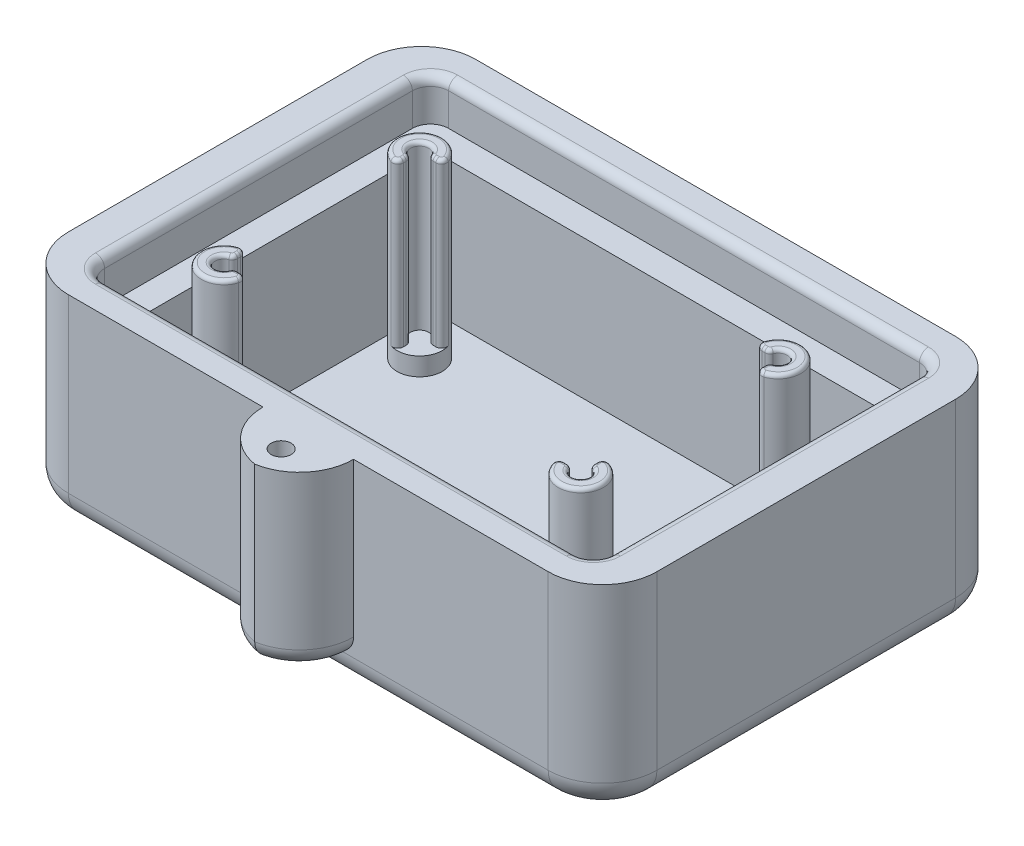
SolidWorks part; units mm, degrees
ref_plane "Front Plane" through (0, 0, 0) normal (0, 0, 1) x (1, 0, 0)
ref_plane "Top Plane" through (0, 0, 0) normal (0, 1, 0) x (1, 0, 0)
ref_plane "Right Plane" through (0, 0, 0) normal (1, 0, 0) x (0, 0, -1)
sketch "Sketch1" plane through (0, 0, 0) normal (0, 1, 0) x (1, 0, 0)
  line L1 (0, 0) -> (82.55, 0)
  line L2 (0, 0) -> (0, 57.15)
  line L3 (0, 57.15) -> (82.55, 57.15)
  line L4 (82.55, 0) -> (82.55, 57.15)
  dimension "D1" = 57.15
  dimension "D2" = 82.55
extrude "Boss-Extrude1" add sketch "Sketch1" along normal blind 27.94
fillet "Fillet2" radius 7.62 4 edges at (82.55, 13.97, -57.15) (82.55, 13.97, 0) (0, 13.97, 0) (0, 13.97, -57.15)
fillet "Fillet3" radius 3.81 8 edges at (80.3182, 0, -54.9182) (82.55, 0, -28.575) (80.3182, 0, -2.2318) (41.275, 0, 0) (2.2318, 0, -2.2318) (0, 0, -28.575) (2.2318, 0, -54.9182) (41.275, 0, -57.15)
sketch "Sketch2" plane through (0, 27.94, 0) normal (0, 1, 0) x (1, 0, 0)
  line L0 (0, 28.575) -> (82.55, 28.575) construction
  line L1 (0, 49.53) -> (0, 7.62) construction
  line L2 (82.55, 7.62) -> (82.55, 49.53) construction
  line L4 (9.525, 8.255) -> (73.025, 8.255)
  line L5 (9.525, 8.255) -> (9.525, 48.895)
  line L6 (9.525, 48.895) -> (73.025, 48.895)
  line L7 (73.025, 8.255) -> (73.025, 48.895)
  line L8 (9.525, 8.255) -> (73.025, 48.895) construction
  line L9 (9.525, 48.895) -> (73.025, 8.255) construction
  point P6 (41.275, 28.575)
  dimension "D1" = 40.64
  dimension "D2" = 63.5
extrude "Cut-Extrude1" cut sketch "Sketch2" against normal blind 25.4
sketch "Sketch7" plane through (0, 27.94, 0) normal (0, 1, 0) x (1, 0, 0)
  line L14 (5.715, 52.705) -> (5.715, 4.445)
  line L15 (5.715, 4.445) -> (76.835, 4.445)
  line L16 (76.835, 4.445) -> (76.835, 52.705)
  line L17 (76.835, 52.705) -> (5.715, 52.705)
  line L18 (5.715, 52.705) -> (5.715, 4.445)
  line L19 (5.715, 4.445) -> (76.835, 4.445)
  line L20 (76.835, 4.445) -> (76.835, 52.705)
  line L21 (76.835, 52.705) -> (5.715, 52.705)
  dimension "D1" = 3.81
sketch "Sketch5" plane through (0, 2.54, 0) normal (0, 1, 0) x (1, 0, 0)
  line L0 (9.525, 48.895) -> (9.525, 8.255) construction
  line L1 (9.525, 8.255) -> (73.025, 8.255) construction
  line L2 (73.025, 48.895) -> (9.525, 48.895) construction
  circle A0 centre (14.605, 42.291) radius 3.175
  circle A1 centre (14.605, 14.859) radius 3.175
  circle A2 centre (64.897, 42.291) radius 3.175
  circle A3 centre (64.8964, 14.605) radius 3.175
  dimension "D5" = 6.35
  dimension "D6" = 6.35
  dimension "D7" = 6.35
  dimension "D8" = 6.35
  dimension "D11" = 6.604
  dimension "D1" = 5.08
  dimension "D2" = 27.432
  dimension "D3" = 27.686
  dimension "D4" = 5.08
  dimension "D9" = 6.604
  dimension "D10" = 50.292
  dimension "D12" = 50.292
sketch "Sketch9" plane through (0, 0, 0) normal (0, 0, 1) x (1, 0, 0)
  line L0 (41.275, 27.94) -> (41.275, 3.81) construction
  line L1 (7.62, 27.94) -> (74.93, 27.94) construction
  line L2 (7.62, 3.81) -> (74.93, 3.81) construction
  line L4 (47.625, 27.94) -> (34.925, 27.94)
  line L5 (47.625, 27.94) -> (47.625, 3.81)
  line L6 (47.625, 3.81) -> (34.925, 3.81)
  line L7 (34.925, 27.94) -> (34.925, 3.81)
  line L8 (47.625, 27.94) -> (34.925, 3.81) construction
  line L9 (47.625, 3.81) -> (34.925, 27.94) construction
  point P6 (41.275, 15.875)
  dimension "D1" = 12.7
extrude "Boss-Extrude5" add sketch "Sketch9" along normal blind 7.62
fillet "Fillet10" radius 7.62 2 edges at (47.625, 15.875, 7.62) (34.925, 15.875, 7.62)
extrude "Cut-Extrude4" cut sketch "Sketch7" against normal blind 5.842
fillet "Fillet12" radius 2.54 4 edges at (76.835, 25.019, -52.705) (76.835, 25.019, -4.445) (5.715, 25.019, -52.705) (5.715, 25.019, -4.445)
fillet "Fillet13" radius 1.27 8 edges at (6.4589, 27.94, -5.1889) (5.715, 27.94, -28.575) (6.4589, 27.94, -51.9611) (41.275, 27.94, -52.705) (76.0911, 27.94, -51.9611) (76.835, 27.94, -28.575) (76.0911, 27.94, -5.1889) (41.275, 27.94, -4.445)
extrude "Boss-Extrude6" add sketch "Sketch5" along normal blind 25.4
sketch "Sketch11" plane through (0, 27.94, 0) normal (0, 1, 0) x (1, 0, 0)
  circle A0 centre (14.605, 14.859) radius 1.27
  circle A1 centre (14.605, 42.291) radius 1.27
  circle A2 centre (64.8964, 14.605) radius 1.27
  circle A3 centre (64.897, 42.291) radius 1.27
  dimension "D1" = 2.54
  dimension "D2" = 2.54
  dimension "D3" = 2.54
  dimension "D4" = 2.54
extrude "Cut-Extrude5" cut sketch "Sketch11" against normal blind 22.86
sketch "Sketch17" plane through (0, 5.08, 0) normal (0, 1, 0) x (1, 0, 0)
  arc A0 (17.78, 42.291) -> (14.605, 39.116) centre (14.605, 42.291) cw
  circle A2 centre (14.605, 42.291) radius 3.175 construction
  arc A5 (61.7214, 14.605) -> (64.8964, 17.78) centre (64.8964, 14.605) cw
  arc A8 (14.605, 18.034) -> (17.78, 14.859) centre (14.605, 14.859) cw
  circle A9 centre (14.605, 14.859) radius 3.175 construction
  circle A10 centre (64.8964, 14.605) radius 3.175 construction
  arc A11 (63.627, 42.291) -> (64.897, 41.021) centre (64.897, 42.291) ccw
  circle A12 centre (64.897, 42.291) radius 1.27 construction
extrude "Cut-Extrude-Thin1" cut sketch "Sketch17" along normal through all thin
sketch "Sketch20" plane through (0, 3.81, 0) normal (0, -1, 0) x (1, 0, 0)
  line L0 (41.275, 7.5134) -> (41.275, 0) construction
  line L3 (34.925, 0) -> (47.625, 0) construction
  circle A0 centre (41.275, 3.81) radius 1.397
  point P6 (41.275, 3.81)
  dimension "D1" = 2.794
extrude "Cut-Extrude6" cut sketch "Sketch20" against normal through all
fillet "Fillet14" radius 2.54 2 edges at (36.7251, 3.81, 4.9187) (45.8249, 3.81, 4.9187)
fillet "Fillet16" radius 0.762 16 edges at (14.605, 16.51, -18.034) (14.605, 16.51, -16.129) (15.875, 16.51, -14.859) (17.78, 16.51, -14.859) (17.78, 16.51, -42.291) (15.875, 16.51, -42.291) (14.605, 16.51, -41.021) (14.605, 16.51, -39.116) (61.722, 16.51, -42.291) (63.627, 16.51, -42.291) (64.897, 16.51, -41.021) (64.897, 16.51, -39.116) (64.8964, 16.51, -17.78) (64.8964, 16.51, -15.875) (63.6264, 16.51, -14.605) (61.7214, 16.51, -14.605)
fillet "Fillet17" radius 0.508 32 edges at (14.4748, 27.94, -16.3167) (16.0627, 27.94, -14.7288) (14.2887, 27.94, -17.7666) (17.5126, 27.94, -14.5427) (13.707, 27.94, -13.961) (12.3599, 27.94, -12.6139) (13.707, 27.94, -43.189) (14.4748, 27.94, -40.8333) (14.2887, 27.94, -39.3834) (12.3599, 27.94, -44.5361) (17.5126, 27.94, -42.6073) (16.0627, 27.94, -42.4212) (65.2133, 27.94, -39.3834) (65.0272, 27.94, -40.8333) (65.795, 27.94, -43.189) (63.4393, 27.94, -42.4212) (61.9894, 27.94, -42.6073) (67.1421, 27.94, -44.5361) (61.9888, 27.94, -14.2887) (63.4386, 27.94, -14.4748) (65.7944, 27.94, -13.707) (65.0265, 27.94, -16.0627) (65.2127, 27.94, -17.5126) (67.1414, 27.94, -12.3599) (16.6916, 27.94, -42.291) (14.605, 27.94, -40.2044) (62.8104, 27.94, -42.291) (64.897, 27.94, -40.2044) (62.8097, 27.94, -14.605) (64.8964, 27.94, -16.6916) (14.605, 27.94, -16.9456) (16.6916, 27.94, -14.859)
equation "\"0.04n\"=0.1"
